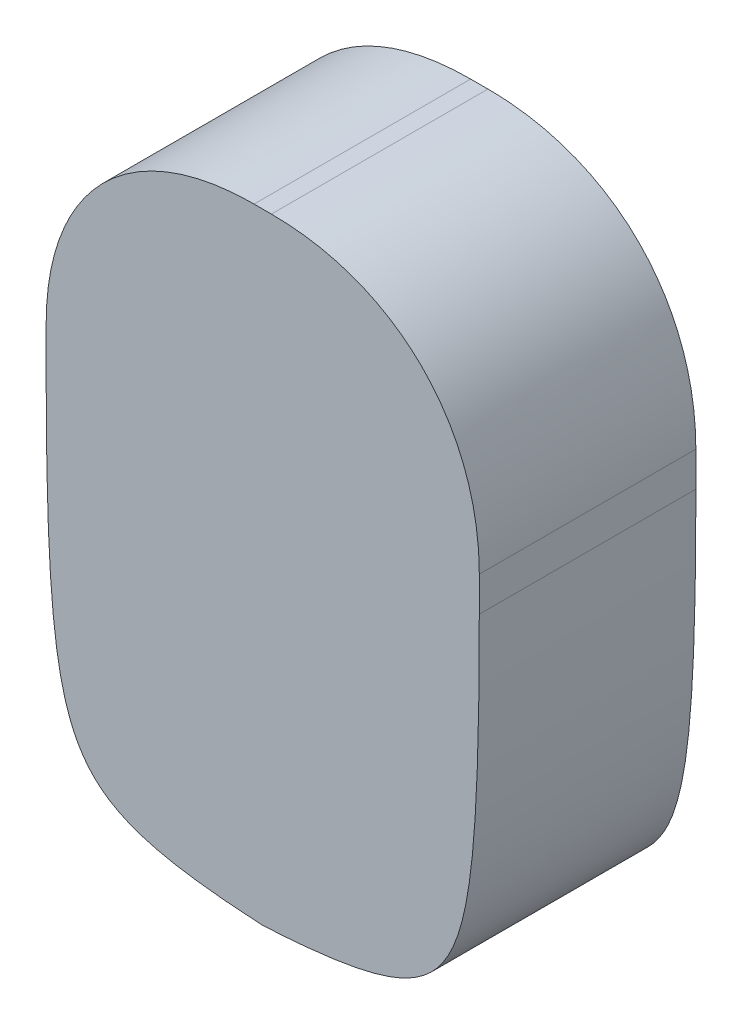
SolidWorks part; units mm, degrees
material "Acrylic (Medium-high impact)"
ref_plane "Front Plane" through (0, 0, 0) normal (0, 0, 1) x (1, 0, 0)
ref_plane "Top Plane" through (0, 0, 0) normal (0, 1, 0) x (1, 0, 0)
ref_plane "Right Plane" through (0, 0, 0) normal (1, 0, 0) x (0, 0, -1)
sketch "Sketch1" plane through (0, 0, 0) normal (0, 0, 1) x (1, 0, 0)
  line L1 (-140.9896, -34.6224) -> (109.0104, -34.6224)
  line L2 (-140.9896, -34.6224) -> (-140.9896, -394.6224)
  line L3 (-140.9896, -394.6224) -> (109.0104, -394.6224)
  line L4 (109.0104, -34.6224) -> (109.0104, -394.6224)
  dimension "D1" = 360
  dimension "D2" = 250
extrude "Boss-Extrude7" add sketch "Sketch1" along normal blind 125
fillet "Fillet5" radius 220 2 edges at (109.0104, -394.6224, 62.5) (-140.9896, -394.6224, 62.5) conic rho 0.75
fillet "Fillet3" radius 120 2 edges at (109.0104, -34.6224, 62.5) (-140.9896, -34.6224, 62.5) conic rho 0.45
